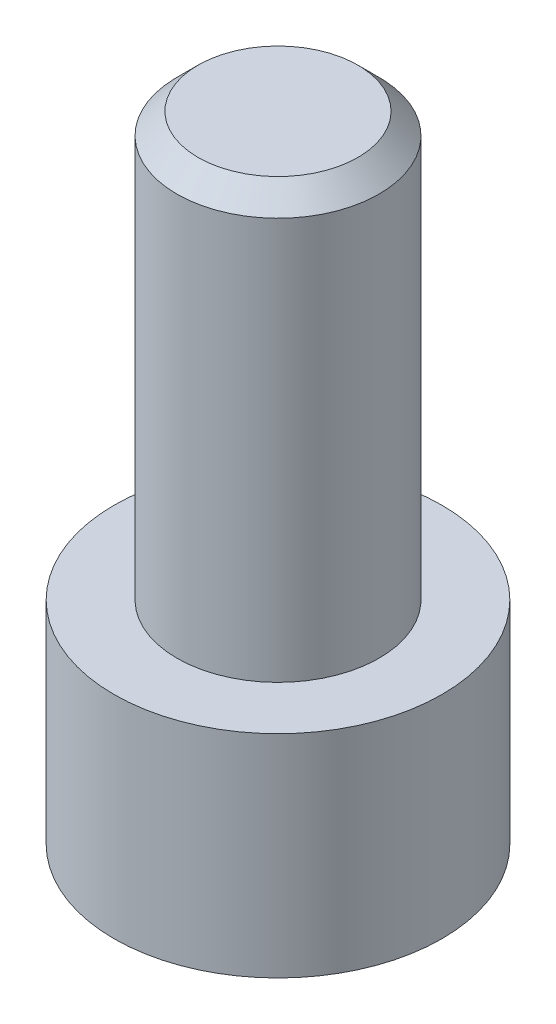
SolidWorks part; units mm, degrees
ref_plane "Front Plane" through (0, 0, 0) normal (0, 0, 1) x (1, 0, 0)
ref_plane "Top Plane" through (0, 0, 0) normal (0, 1, 0) x (1, 0, 0)
ref_plane "Right Plane" through (0, 0, 0) normal (1, 0, 0) x (0, 0, -1)
sketch "Sketch1" plane through (0, 0, 0) normal (0, 1, 0) x (1, 0, 0)
  line L1 (4.4745, 0) -> (2.2372, 3.875) construction
  line L2 (2.2372, 3.875) -> (-2.2372, 3.875) construction
  line L3 (-2.2372, 3.875) -> (-4.4745, 0) construction
  line L4 (-4.4745, 0) -> (-2.2372, -3.875) construction
  line L5 (-2.2372, -3.875) -> (2.2372, -3.875) construction
  line L6 (2.2372, -3.875) -> (4.4745, 0) construction
  circle A0 centre (0, 0) radius 3.875
  dimension "D1" = 7.75
extrude "Boss-Extrude1" add sketch "Sketch1" along normal blind 15
sketch "Sketch2" plane through (0, 15, 0) normal (0, 1, 0) x (1, 0, 0)
  circle A0 centre (0, 0) radius 2.39
  dimension "D1" = 4.78
extrude "Cut-Extrude1" cut sketch "Sketch2" against normal blind 10 flip side to cut
ref_axis "Axis1" through (0, 5, 0) along (0, 1, 0)
chamfer "Chamfer1" distance 0.5 angle 45 1 edges at (0, 15, 2.39)
sketch "Sketch5" plane through (0, 15, 0) normal (0, 1, 0) x (1, 0, 0)
  circle A0 centre (0, 0) radius 2.39
  dimension "D1" = 4.78
curve "Helix/Spiral1" pitch 0.7 height 25 turns 35.7143
ref_plane "Plane1" through (0, 15, 2.39) normal (-0.9989, -0.0466, 0) x (0, 0, 1)
sketch "Sketch8" plane through (0, 0, 0) normal (0, -1, 0) x (1, 0, 0)
  line L1 (2.6443, 0) -> (1.3221, 2.29)
  line L2 (1.3221, 2.29) -> (-1.3221, 2.29)
  line L3 (-1.3221, 2.29) -> (-2.6443, 0)
  line L4 (-2.6443, 0) -> (-1.3221, -2.29)
  line L5 (-1.3221, -2.29) -> (1.3221, -2.29)
  line L6 (1.3221, -2.29) -> (2.6443, 0)
  circle A0 centre (0, 0) radius 2.29 construction
  dimension "D1" = 4.58
extrude "Cut-Extrude2" cut sketch "Sketch8" against normal blind 3.36
